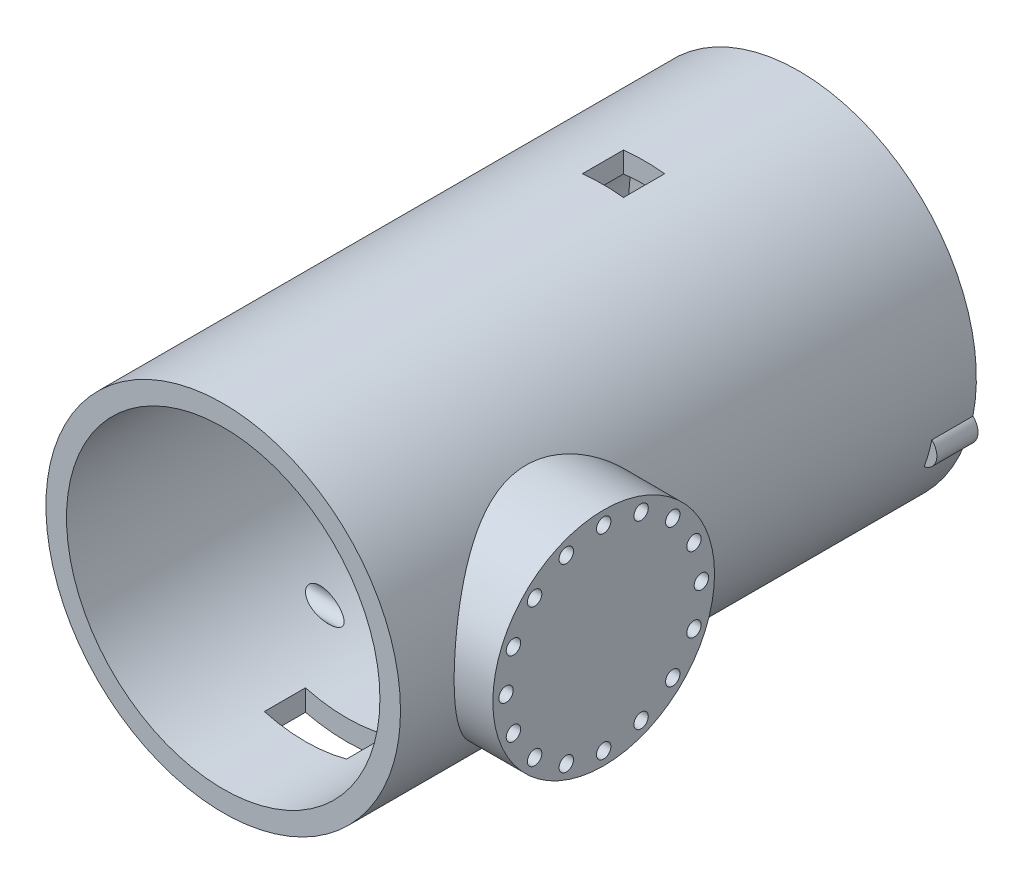
SolidWorks part; units mm, degrees
other "Markup1"
sketch "Sketch14" plane through (-43.1, 43.1, 140) normal (-0.1765, 0.0048, 0.9843) x (0.9842, -0.0149, 0.1765)
other "Markup2"
sketch "Sketch23" plane through (45.1, -43.1, 140) normal (0.9491, -0.0629, 0.3087) x (0.311, 0.031, -0.9499)
ref_plane "Front Plane" through (0, 0, 0) normal (0, 0, 1) x (1, 0, 0)
ref_plane "Top Plane" through (0, 0, 0) normal (0, 1, 0) x (1, 0, 0)
ref_plane "Right Plane" through (0, 0, 0) normal (1, 0, 0) x (0, 0, -1)
sketch "Sketch1" plane through (0, 0, 0) normal (0, 0, 1) x (1, 0, 0)
  circle A1 centre (0, 0) radius 43.1
  dimension "D1" = 86.2
extrude "Main Body" add sketch "Sketch1" along normal blind 140
ref_plane "Plane1" through (0, 43.1, 0) normal (0, 1, 0) x (1, 0, 0)
sketch "Sketch6" plane through (0, 43.1, 0) normal (0, 1, 0) x (1, 0, 0)
  line L2 (-5, -47.7) -> (5, -47.7)
  line L3 (-5, -47.7) -> (-5, -37.7)
  line L4 (-5, -37.7) -> (5, -37.7)
  line L5 (5, -47.7) -> (5, -37.7)
  line L6 (-5, -47.7) -> (5, -37.7) construction
  line L7 (-5, -37.7) -> (5, -47.7) construction
  point P2 (0, -42.7)
  dimension "D2" = 10
  dimension "D1" = 42.7
  dimension "D3" = 10
extrude "Cut-Extrude3" cut sketch "Sketch6" against normal through all
ref_plane "Plane2" through (52.5, 0, 0) normal (1, 0, 0) x (0, 0, -1)
sketch "Sketch8" plane through (52.5, 0, 0) normal (1, 0, 0) x (0, 0, -1)
  circle A0 centre (-100, 0) radius 26.95
  dimension "D1" = 53.9
  dimension "D2" = 100
extrude "Boss-Extrude2" add sketch "Sketch8" against normal blind 20
mirror "Mirror1" [suppressed] about plane through (0, 0, 0) normal (1, 0, 0)
sketch "Sketch5" plane through (0, 0, 140) normal (0, 0, 1) x (1, 0, 0)
  circle A0 centre (0, 0) radius 31.75
  dimension "D1" = 63.5
extrude "Hole 1" cut sketch "Sketch5" against normal through all
sketch "Sketch10" plane through (0, 0, 0) normal (0, 1, 0) x (1, 0, 0)
  line L0 (43.1, 0) -> (-43.1, 0) construction
  line L1 (-10, -120) -> (10, -120)
  line L2 (-10, -120) -> (-10, -110)
  line L3 (-10, -110) -> (10, -110)
  line L4 (10, -120) -> (10, -110)
  line L5 (-10, -120) -> (10, -110) construction
  line L6 (-10, -110) -> (10, -120) construction
  point P0 (0, -115)
  point P7 (-10, -115)
  dimension "D1" = 110
  dimension "D2" = 10
  dimension "D3" = 20
extrude "Motor Wire Hole" cut sketch "Sketch10" against normal through all
sketch "Sketch27" plane through (0, 0, 0) normal (1, 0, 0) x (0, 0, -1)
  line L1 (-100, -36.5) -> (-60, -36.5)
  line L2 (-100, -36.5) -> (-100, -27.5)
  line L3 (-100, -27.5) -> (-60, -27.5)
  line L4 (-60, -36.5) -> (-60, -27.5)
  dimension "D1" = 60
  dimension "D2" = 27.5
  dimension "D3" = 40
  dimension "D4" = 9
extrude "Boss-Extrude9" add sketch "Sketch27" along normal blind 33 and the other way blind 33
sketch "Sketch11" plane through (0, 0, 0) normal (1, 0, 0) x (0, 0, -1)
  circle A0 centre (-65, -32) radius 2.5
  circle A1 centre (-95, -32) radius 2.5
  dimension "D3" = 5
  dimension "D1" = 65
  dimension "D2" = 32
  dimension "D4" = 30
extrude "Cut-Extrude6" cut sketch "Sketch11" against normal through all both and the other way through all
sketch "Sketch28" plane through (-33, 0, 0) normal (-1, 0, 0) x (0, 0, 1)
  line L0 (62.9793, -28.5) -> (67.0207, -28.5)
  line L1 (67.0207, -28.5) -> (69.0415, -32)
  line L2 (69.0415, -32) -> (67.0207, -35.5)
  line L3 (67.0207, -35.5) -> (62.9793, -35.5)
  line L4 (62.9793, -35.5) -> (60.9585, -32)
  line L6 (60.9585, -32) -> (62.9793, -28.5)
  line L7 (92.9793, -28.5) -> (97.0207, -28.5)
  line L8 (97.0207, -28.5) -> (99.0415, -32)
  line L9 (99.0415, -32) -> (97.0207, -35.5)
  line L10 (97.0207, -35.5) -> (92.9793, -35.5)
  line L11 (92.9793, -35.5) -> (90.9585, -32)
  line L12 (90.9585, -32) -> (92.9793, -28.5)
  circle A0 centre (65, -32) radius 3.5 construction
  circle A1 centre (65, -32) radius 2.5 construction
  circle A2 centre (95, -32) radius 3.5 construction
  circle A3 centre (95, -32) radius 2.5 construction
  dimension "D1" = 7
  dimension "D2" = 7
extrude "Cut-Extrude7" cut sketch "Sketch28" against normal blind 3
sketch "Sketch29" plane through (33, 0, 0) normal (1, 0, 0) x (0, 0, -1)
  circle A0 centre (-95, -32) radius 3.5
  circle A1 centre (-65, -32) radius 3.5
  dimension "D1" = 7
extrude "Cut-Extrude8" cut sketch "Sketch29" against normal blind 4
sketch "Sketch2" plane through (0, 0, 140) normal (0, 0, 1) x (1, 0, 0)
  circle A0 centre (0, 0) radius 38.1
  dimension "D1" = 76.2
extrude "Cut-Extrude5" cut sketch "Sketch2" against normal blind 135
sketch "Sketch9" plane through (0, 0, 5) normal (0, 0, 1) x (1, 0, 0)
  circle A0 centre (0, 0) radius 38.1
  circle A1 centre (0, 0) radius 36.44
  dimension "D1" = 76.2
  dimension "D2" = 1.66
extrude "Boss-Extrude3" add sketch "Sketch9" along normal blind 10
sketch "Sketch30" plane through (52.5, 0, 0) normal (1, 0, 0) x (0, 0, -1)
  line L0 (-100, 23.75) -> (-100, 0) construction
  circle A0 centre (-100, 0) radius 23.75 construction
  circle A1 centre (-100, 23.75) radius 1.75
  circle A2 centre (-90.9113, 21.9421) radius 1.75
  circle A3 centre (-83.2062, 16.7938) radius 1.75
  circle A4 centre (-78.0579, 9.0887) radius 1.75
  circle A5 centre (-76.25, 0) radius 1.75
  circle A6 centre (-78.0579, -9.0887) radius 1.75
  circle A7 centre (-83.2062, -16.7938) radius 1.75
  circle A8 centre (-90.9113, -21.9421) radius 1.75
  circle A9 centre (-100, -23.75) radius 1.75
  circle A10 centre (-109.0887, -21.9421) radius 1.75
  circle A11 centre (-116.7938, -16.7938) radius 1.75
  circle A12 centre (-121.9421, -9.0887) radius 1.75
  circle A13 centre (-123.75, 0) radius 1.75
  circle A14 centre (-121.9421, 9.0887) radius 1.75
  circle A15 centre (-116.7938, 16.7938) radius 1.75
  circle A16 centre (-109.0887, 21.9421) radius 1.75
  point P5 (0, 0)
  point P6 (0, 0)
  point P38 (-100, 0)
  dimension "D1" = 47.5
  dimension "D2" = 3.5
  dimension "D3" = 16
extrude "Cut-Extrude9" cut sketch "Sketch30" against normal up to surface (22.7083 mm away) up to face at (38.1, 0, 15)
sketch "Sketch31" plane through (52.5, 0, 0) normal (1, 0, 0) x (0, 0, -1)
  line L0 (0, -43.1) -> (0, 43.1) construction
  line L1 (0, -15) -> (-10, -15)
  line L2 (0, -15) -> (0, -7.5)
  line L3 (0, -7.5) -> (-10, -7.5)
  line L4 (-10, -15) -> (-10, -7.5)
  dimension "D1" = 15
  dimension "D2" = 7.5
  dimension "D3" = 10
extrude "Boss-Extrude10" add sketch "Sketch31" against normal up to body from offset 9 offset against normal yes
sketch "Sketch32" plane through (0, 0, 0) normal (0, 0, -1) x (-1, 0, 0)
  line L0 (-43.5, -11.25) -> (-29.6901, -11.25) construction
  line L1 (-43.5, -15) -> (-43.5, -7.5) construction
  line L3 (-42.4424, -7.5) -> (-43.5, -7.5) construction
  line L5 (-43.5, -15) -> (-43.5, -7.5)
  line L6 (-43.5, -7.5) -> (-42.4424, -7.5)
  circle A0 centre (0, 0) radius 31.75 construction
  arc A2 (-40.4056, -15) -> (-42.4424, -7.5) centre (0, 0) ccw construction
  arc A3 (-40.4056, -15) -> (-42.2658, -8.4385) centre (-39.6806, -11.25) cw
  arc A4 (-42.2658, -8.4385) -> (-42.4424, -7.5) centre (0, 0) cw
  point P15 (0, 0)
  line M3 (-42.4424, -7.5) -> (-43.5, -7.5)
  line M4 (-43.5, -7.5) -> (-43.5, -15)
  line M5 (-43.5, -15) -> (-40.4056, -15)
extrude "Cut-Extrude10" cut sketch "Sketch32" against normal up to surface (10 mm away) contours M4 M3 | L5 M5 region at (43.0347, -8.5479, 0) region at (42.7123, -14.1508, 0) up to face at (42.5043, -11.2615, 10)
